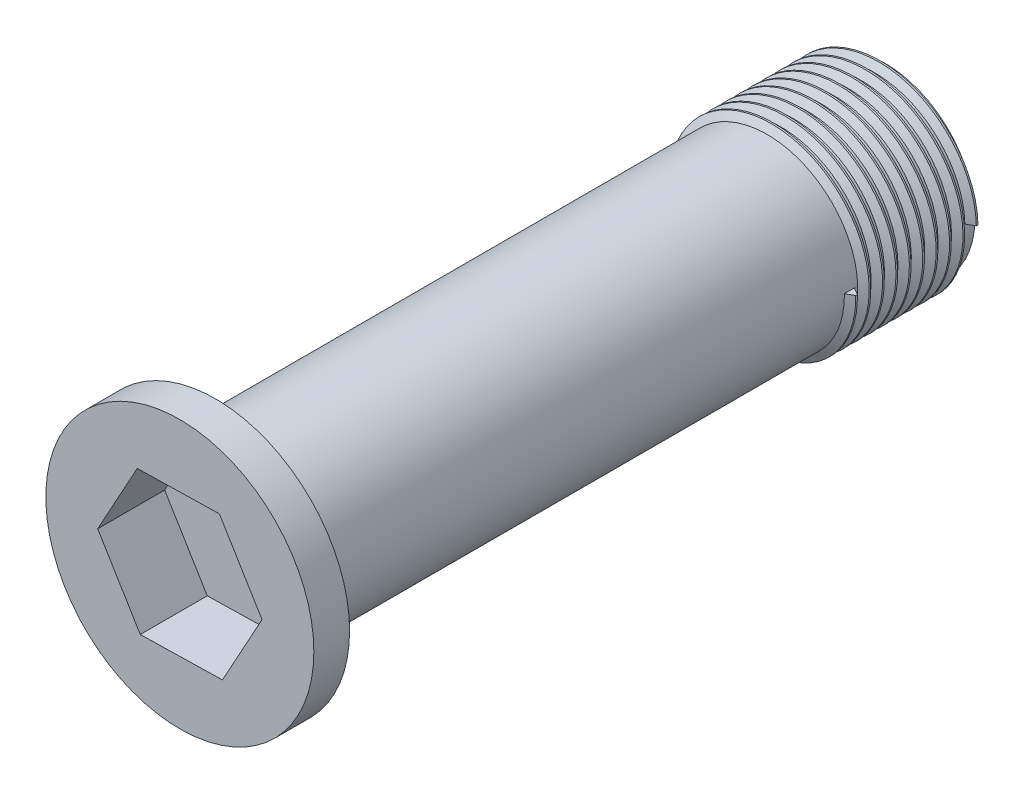
SolidWorks part; units mm, degrees
material "AISI 304"
ref_plane "Alzado" through (0, 0, 0) normal (0, 0, 1) x (1, 0, 0)
ref_plane "Planta" through (0, 0, 0) normal (0, 1, 0) x (1, 0, 0)
ref_plane "Vista lateral" through (0, 0, 0) normal (1, 0, 0) x (0, 0, -1)
ref_plane "Plano1" through (0, 0, 51.9) normal (0, 0, 1) x (1, 0, 0)
sketch "Sk_Cana" plane through (0, 0, 51.9) normal (0, 0, 1) x (1, 0, 0)
  circle A0 centre (0, 0) radius 2
extrude "Cana" add sketch "Sk_Cana" along normal blind 15 from offset 2
ref_plane "Plano2" through (0, 0, 68.9) normal (0, 0, 1) x (1, 0, 0)
sketch "Sk_Cabeza" plane through (0, 0, 68.9) normal (0, 0, 1) x (1, 0, 0)
  circle A0 centre (0, 0) radius 3
extrude "Cabeza" add sketch "Sk_Cabeza" along normal blind 0.8
sketch "Croquis1" plane through (0, 0, 53.9) normal (0, 0, -1) x (-1, 0, 0)
  circle A1 centre (0, 0) radius 2
  circle A2 centre (0, 0) radius 2
  dimension "D1" = 0
thread "Rosca1" pitch 0.3 method extrude profile "Perfil de rosca2" start angle 0, offset 0, length 0, pitch 0.3, diameter 4
ref_plane "Plano4" through (2, 0, 53.9) normal (0, -1, 0) x (1, 0, 0)
sketch "Perfil de rosca2" plane through (2, 0, 53.9) normal (0, -1, 0) x (1, 0, 0)
  line L0 (0, 0) -> (0, 0.3) construction
  line L1 (0, 0) -> (0.1624, 0.0937)
  line L2 (0.1624, 0.0937) -> (0.1624, 0.1312)
  line L3 (0.1624, 0.1312) -> (0, 0.225)
  line L4 (0.1624, 0.1125) -> (0, 0.1125) construction
  line L11 (0, 0) -> (0, 0.225)
  point P2 (0, 0)
  dimension "Pitch" = 0.3
  dimension "Profile_Angle" = 60
  dimension "Profile_Land" = 0.0375
  dimension "Profile_Height" = 0.1624
sketch "Croquis9" plane through (0, 0, 69.7) normal (0, 0, 1) x (1, 0, 0)
  line L1 (0.886, 1.6125) -> (-0.9535, 1.5735)
  line L2 (-0.9535, 1.5735) -> (-1.8395, -0.039)
  line L3 (-1.8395, -0.039) -> (-0.886, -1.6125)
  line L4 (-0.886, -1.6125) -> (0.9535, -1.5735)
  line L5 (0.9535, -1.5735) -> (1.8395, 0.039)
  line L6 (1.8395, 0.039) -> (0.886, 1.6125)
  circle A0 centre (0, 0) radius 1.5934 construction
extrude "Cortar-Extruir1" cut sketch "Croquis9" against normal blind 1.5
